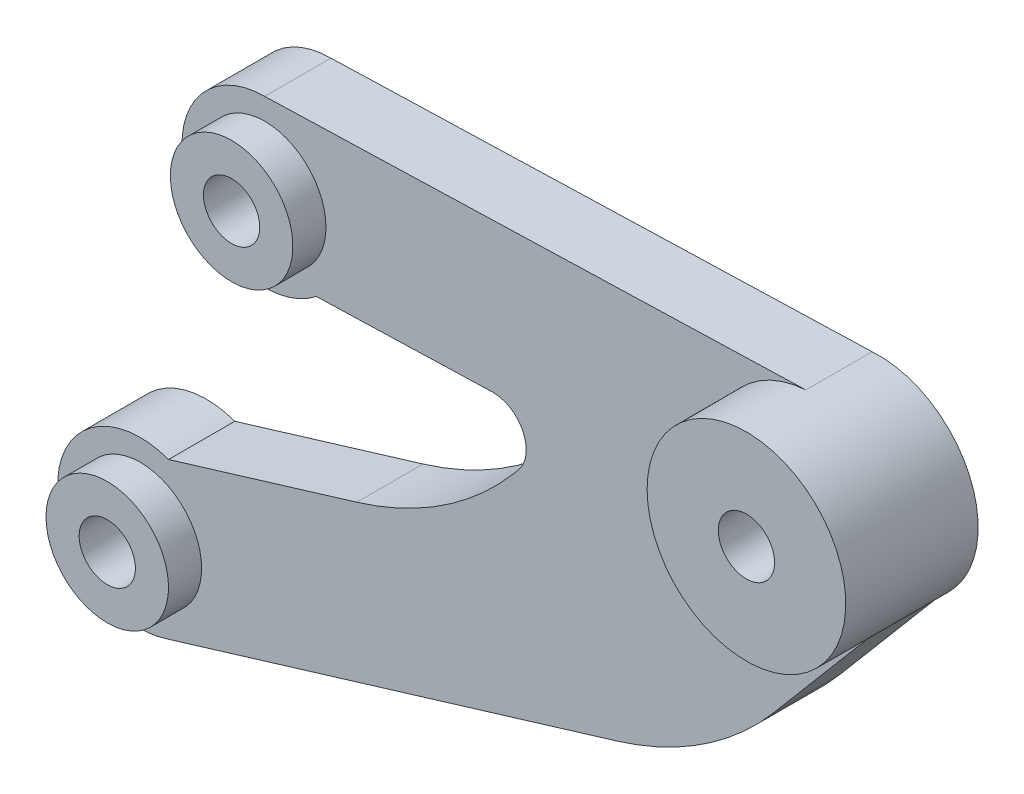
SolidWorks part; units mm, degrees
ref_plane "Front Plane" through (0, 0, 0) normal (0, 0, 1) x (1, 0, 0)
ref_plane "Top Plane" through (0, 0, 0) normal (0, 1, 0) x (1, 0, 0)
ref_plane "Right Plane" through (0, 0, 0) normal (1, 0, 0) x (0, 0, -1)
sketch "Sketch2" plane through (0, 0, 0) normal (0, 0, 1) x (1, 0, 0)
  line L0 (0, 0) -> (0, 21.6008) construction
  line L1 (40.6129, 21.6008) -> (0, 21.6008) construction
  line L2 (0, 0) -> (0, 21.6008) construction
  line L3 (0, 21.6008) -> (7.5129, 21.6008) construction
  line L4 (1.5758, -4.7452) -> (34.4569, 5.2326)
  line L5 (34.4569, 5.2326) -> (44.2966, 16.8647)
  line L6 (7.5129, 26.6008) -> (40.2038, 27.5868)
  line L10 (25.7338, 18.1463) -> (18.7287, 9.8651)
  line L11 (18.7287, 9.8651) -> (1.7066, 4.6997)
  line L12 (10.6292, 17.6907) -> (25.7338, 18.1463)
  circle A0 centre (0, 0) radius 1.7
  circle A1 centre (40.6129, 21.6008) radius 1.7
  circle A2 centre (7.5129, 21.6008) radius 1.7
  arc A3 (1.7066, 4.6997) -> (1.5758, -4.7452) centre (0, 0) ccw
  arc A4 (44.2966, 16.8647) -> (40.2038, 27.5868) centre (40.6129, 21.6008) ccw
  arc A5 (7.5129, 26.6008) -> (10.6292, 17.6907) centre (7.5129, 21.6008) ccw
  dimension "D1" = 3.4
  dimension "D2" = 3.4
  dimension "D3" = 3.4
  dimension "D8" = 10
  dimension "D9" = 12
  dimension "D10" = 10
  dimension "D4" = 46
  dimension "D5" = 33.1
  dimension "D7" = 22.87
  dimension "D11" = 9
  dimension "D12" = 9
  dimension "D13" = 15
extrude "Boss-Extrude1" add sketch "Sketch2" along normal blind 2 and the other way blind 2 contours L6 A5 A3 L4 L5 A4 A0 A1 A2 region at (22.1673, 13.7132, 0)
fillet "Fillet1" radius 20 2 edges at (34.4569, 5.2326, 0) (18.7287, 9.8651, 0)
sketch "Sketch3" plane through (0, 0, 2) normal (0, 0, 1) x (1, 0, 0)
  line L0 (44.2966, 16.8647) -> (30.687, 0.776)
  line L1 (38.2697, 9.7399) -> (44.2966, 16.8647) construction
  line L2 (30.687, 0.776) -> (37.0794, -4.6314)
  line L3 (37.0794, -4.6314) -> (43.0769, 2.4586)
  line L4 (44.2966, 16.8647) -> (50.689, 11.4573)
  line L5 (50.689, 11.4573) -> (44.6915, 4.3673)
  line L6 (43.0769, 2.4586) -> (32.5644, 0.4977)
  line L7 (32.5644, 0.4977) -> (44.8824, 15.0595)
  line L8 (44.8824, 15.0595) -> (44.6915, 4.3673)
  line L9 (32.5644, 0.4977) -> (31.9186, -0.2658) construction
  line L10 (44.8824, 15.0595) -> (45.5282, 15.8229) construction
  dimension "D1" = 1
  dimension "D2" = 2.5
extrude "Boss-Extrude2" [suppressed] add sketch "Sketch3" against normal up to surface (10 mm away)
fillet "Fillet2" [suppressed] radius 1
sketch "Sketch4" plane through (0, 0, 2) normal (0, 0, 1) x (1, 0, 0)
  line L7 (38.2697, 9.7399) -> (44.2966, 16.8647) construction
  line L8 (0, 0) -> (50000, 0) construction
  line L17 (44.2966, 16.8647) -> (44.8756, 15.9348)
  line L18 (40.6475, 27.6007) -> (47.8271, 27.6007)
  line L19 (47.8271, 27.6007) -> (51.8229, 19.889)
  line L20 (51.0994, 17.0478) -> (51.7638, 16.0989)
  line L21 (48.2447, 15.0489) -> (48.9091, 14.1)
  line L22 (48.3535, 17.9314) -> (-28630.4683, 40975.5336) construction
  arc A0 (40.6475, 27.6007) -> (44.2966, 16.8647) centre (40.6129, 21.6008) cw
  arc A1 (44.2966, 16.8647) -> (40.2038, 27.5868) centre (40.6129, 21.6008) ccw construction
  arc A3 (48.2447, 15.0489) -> (51.0994, 17.0478) centre (48.2713, 18.0488) ccw
  arc A4 (44.8756, 15.9348) -> (51.7638, 16.0989) centre (48.2713, 18.0488) ccw
  arc A5 (48.9091, 14.1) -> (51.8229, 19.889) centre (48.2713, 18.0488) ccw
  dimension "D1" = 6
  dimension "D2" = 8
  dimension "D3" = 55
extrude "Boss-Extrude3" [suppressed] add sketch "Sketch4" against normal up to surface (4 mm away)
fillet "Fillet3" [suppressed] radius 6
sketch "Sketch7" plane through (0, 0, 2) normal (0, 0, -1) x (-1, 0, 0)
  circle A0 centre (-40.6129, 21.6008) radius 1.7
  circle A1 centre (-40.6129, 21.6008) radius 6
  arc A2 (-40.2038, 27.5868) -> (-44.2966, 16.8647) centre (-40.6129, 21.6008) ccw construction
  dimension "D1" = 3.4
extrude "Boss-Extrude4" add sketch "Sketch7" against normal blind 4
sketch "Sketch8" plane through (0, 0, 2) normal (0, 0, -1) x (-1, 0, 0)
  circle A0 centre (-7.5129, 21.6008) radius 1.7
  circle A1 centre (-7.5129, 21.6008) radius 3.7
  circle A2 centre (0, 0) radius 1.7
  circle A3 centre (0, 0) radius 3.7
  dimension "D1" = 2
  dimension "D2" = 2
  dimension "D3" = 3.4
  dimension "D4" = 3.4
extrude "Boss-Extrude5" add sketch "Sketch8" against normal blind 2
fillet "Fillet4" radius 2 1 edges at (25.7338, 18.1463, 0)
